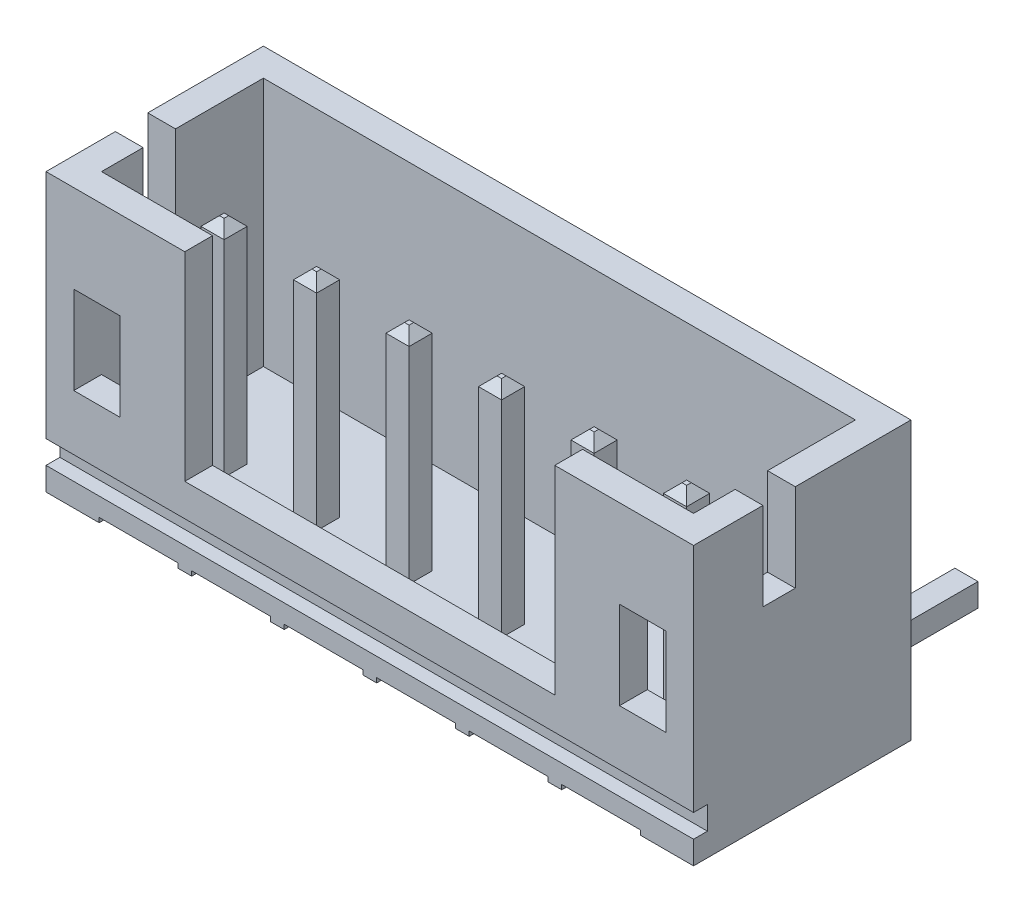
SolidWorks part; units mm, degrees
material "45"
ref_plane "前视基准面" through (0, 0, 0) normal (0, 0, 1) x (1, 0, 0)
ref_plane "上视基准面" through (0, 0, 0) normal (0, 1, 0) x (1, 0, 0)
ref_plane "右视基准面" through (0, 0, 0) normal (1, 0, 0) x (0, 0, -1)
sketch "草图1" plane through (0, 0, 0) normal (0, 1, 0) x (1, 0, 0)
  line L1 (-7, 2.35) -> (7, 2.35)
  line L2 (-7, 2.35) -> (-7, -2.35)
  line L3 (-7, -2.35) -> (7, -2.35)
  line L4 (7, 2.35) -> (7, -2.35)
  line L5 (-7, 2.35) -> (7, -2.35) construction
  line L6 (-7, -2.35) -> (7, 2.35) construction
  point P0 (0, 0)
  dimension "D1" = 14
  dimension "D2" = 4.7
extrude "凸台-拉伸1" add sketch "草图1" along normal blind 6
shell "抽壳1" thickness 0.6 removed face at (0, 6, 0)
sketch "草图2" plane through (0, 0, 2.35) normal (0, 0, 1) x (1, 0, 0)
  line L0 (-7, 6) -> (7, 6) construction
  line L1 (-4, 6) -> (4, 6)
  line L2 (-4, 6) -> (-4, 1.7)
  line L3 (-4, 1.7) -> (4, 1.7)
  line L4 (4, 6) -> (4, 1.7)
  line L5 (-7, 0) -> (7, 0) construction
  dimension "D1" = 8
  dimension "D2" = 4
  dimension "D3" = 1.7
extrude "切除-拉伸1" cut sketch "草图2" against normal blind 1
sketch "草图3" plane through (0, 0, 2.35) normal (0, 0, 1) x (1, 0, 0)
  line L0 (-6.4, 6) -> (-6.4, 0.6) construction
  line L1 (-6.4, 4.1) -> (-5.4, 4.1)
  line L2 (-6.4, 4.1) -> (-6.4, 2.2)
  line L3 (-6.4, 2.2) -> (-5.4, 2.2)
  line L4 (-5.4, 4.1) -> (-5.4, 2.2)
  line L5 (-4, 1.7) -> (4, 1.7) construction
  dimension "D1" = 1
  dimension "D2" = 1.9
  dimension "D3" = 0.5
extrude "切除-拉伸2" cut sketch "草图3" against normal blind 1
mirror "镜向1" about plane through (0, 0, 0) normal (1, 0, 0) of "切除-拉伸2"
sketch "草图4" plane through (-7, 0, 0) normal (-1, 0, 0) x (0, 0, 1)
  line L0 (-2.35, 6) -> (2.35, 6) construction
  line L1 (0.85, 6) -> (0.15, 6)
  line L2 (0.85, 6) -> (0.85, 4.1)
  line L3 (0.85, 4.1) -> (0.15, 4.1)
  line L4 (0.15, 6) -> (0.15, 4.1)
  line L5 (-2.35, 6) -> (-2.35, 0) construction
  dimension "D1" = 3.2
  dimension "D2" = 0.7
  dimension "D3" = 1.9
extrude "切除-拉伸3" cut sketch "草图4" against normal up to surface (14 mm away) up to face at (7, 3, 0)
sketch "草图5" plane through (0, 0, 2.35) normal (0, 0, 1) x (1, 0, 0)
  line L0 (-7, 0) -> (7, 0) construction
  line L1 (-5.85, 0) -> (-4.15, 0)
  line L2 (-5.85, 0) -> (-5.85, 0.1)
  line L3 (-5.85, 0.1) -> (-4.15, 0.1)
  line L4 (-4.15, 0) -> (-4.15, 0.1)
  line L5 (-7, 6) -> (-7, 0) construction
  dimension "D1" = 0.1
  dimension "D2" = 1.7
  dimension "D3" = 1.15
extrude "切除-拉伸4" cut sketch "草图5" against normal up to surface (4.7 mm away) up to face at (0, 3, -2.35)
pattern_linear "阵列(线性)1" count 6 spacing 2 along (1, 0, 0) of "切除-拉伸4"
ref_plane "基准面1" through (5, 0, 0) normal (1, 0, 0) x (0, 0, -1)
sketch "草图7" plane through (0, 0, -2.35) normal (0, 0, -1) x (-1, 0, 0)
  line L1 (-5.85, 0.1) -> (-4.15, 0.1)
  line L2 (-5.85, 0.1) -> (-5.85, 0.5)
  line L3 (-5.85, 0.5) -> (-4.15, 0.5)
  line L4 (-4.15, 0.1) -> (-4.15, 0.5)
  dimension "D1" = 0.4
  dimension "D2" = 1.7
extrude "切除-拉伸5" cut sketch "草图7" against normal blind 3.1
sketch "草图8" plane through (-7, 0, 0) normal (-1, 0, 0) x (0, 0, 1)
  line L0 (2.35, 6) -> (2.35, 0) construction
  line L1 (2.35, 0.5) -> (2.05, 0.5)
  line L2 (2.35, 0.5) -> (2.35, 1)
  line L3 (2.35, 1) -> (2.05, 1)
  line L4 (2.05, 0.5) -> (2.05, 1)
  line L5 (-2.35, 0) -> (2.35, 0) construction
  dimension "D1" = 0.5
  dimension "D2" = 0.5
  dimension "D3" = 0.3
extrude "切除-拉伸6" cut sketch "草图8" against normal up to surface (14 mm away) up to face at (7, 4.025, 0.25)
pattern_linear "阵列(线性)2" count 6 spacing 2 along (-1, 0, 0) of "切除-拉伸5"
sketch "草图6" plane through (5, 0, 0) normal (1, 0, 0) x (0, 0, -1)
  line L0 (-0.5, 5.25) -> (-0.5, 0.25)
  line L1 (-0.5, 0.25) -> (5.75, 0.25)
  line L2 (-2.35, 0) -> (2.35, 0) construction
  line L5 (-0.85, 6) -> (-0.85, 4.1) construction
  dimension "D1" = 5.25
  dimension "D2" = 0.25
  dimension "D3" = 0.35
  dimension "D4" = 6.25
extrude "拉伸-薄壁1" add sketch "草图6" along normal mid plane 0.5 thin thin type mid plane wall 0.5
pattern_linear "阵列(线性)3" count 6 spacing 2 along (-1, 0, 0) of "拉伸-薄壁1"
fillet "圆角1" radius 0.1 6 edges at (5, 0, 0.75) (-5, 0, 0.75) (-3, 0, 0.75) (-1, 0, 0.75) (1, 0, 0.75) (3, 0, 0.75)
chamfer "倒角1" distance 0.2 angle 45 48 edges at (-5, 0, -5.75) (-4.75, 0.25, -5.75) (-5, 0.5, -5.75) (-5.25, 0.25, -5.75) (-3, 0, -5.75) (-2.75, 0.25, -5.75) (-3, 0.5, -5.75) (-3.25, 0.25, -5.75) (-1, 0, -5.75) (-0.75, 0.25, -5.75) (-1, 0.5, -5.75) (-1.25, 0.25, -5.75) (1, 0, -5.75) (1.25, 0.25, -5.75) (1, 0.5, -5.75) (0.75, 0.25, -5.75) (3, 0, -5.75) (3.25, 0.25, -5.75) (3, 0.5, -5.75) (2.75, 0.25, -5.75) (5, 0, -5.75) (5.25, 0.25, -5.75) (5, 0.5, -5.75) (4.75, 0.25, -5.75) (-5, 5.25, 0.25) (-4.75, 5.25, 0.5) (-5, 5.25, 0.75) (-5.25, 5.25, 0.5) (-3, 5.25, 0.25) (-2.75, 5.25, 0.5) (-3, 5.25, 0.75) (-3.25, 5.25, 0.5) (-1, 5.25, 0.25) (-0.75, 5.25, 0.5) (-1, 5.25, 0.75) (-1.25, 5.25, 0.5) (1, 5.25, 0.25) (1.25, 5.25, 0.5) (1, 5.25, 0.75) (0.75, 5.25, 0.5) (3, 5.25, 0.25) (3.25, 5.25, 0.5) (3, 5.25, 0.75) (2.75, 5.25, 0.5) (5, 5.25, 0.25) (5.25, 5.25, 0.5) (5, 5.25, 0.75) (4.75, 5.25, 0.5)
sketch "草图9" plane through (0, 0, -5.75) normal (0, 0, -1) x (-1, 0, 0)
  line L0 (-5, 0.275) -> (-5, -0.275) construction
  circle A0 centre (-5, 0.25) radius 0.0296
  circle A1 centre (5, 0.25) radius 0.0222
extrude "切除-拉伸7" cut sketch "草图9" against normal blind 2
